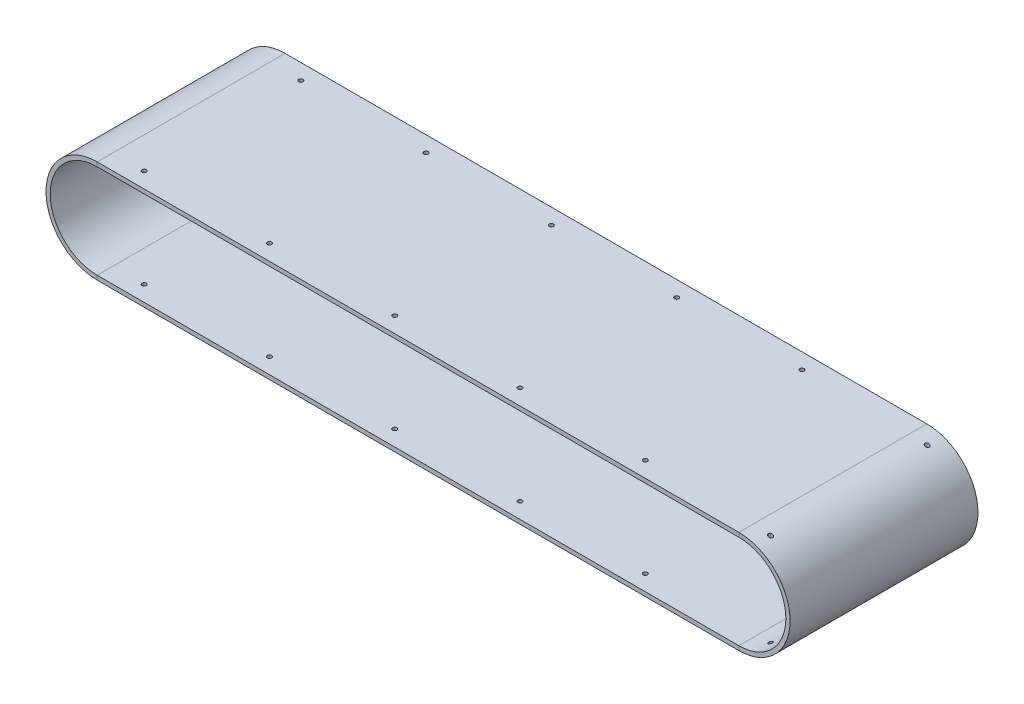
SolidWorks part; units mm, degrees
ref_plane "Front Plane" through (0, 0, 0) normal (0, 0, 1) x (1, 0, 0)
ref_plane "Top Plane" through (0, 0, 0) normal (0, 1, 0) x (1, 0, 0)
ref_plane "Right Plane" through (0, 0, 0) normal (1, 0, 0) x (0, 0, -1)
sketch "Sketch1" plane through (0, 0, 0) normal (0, 0, 1) x (1, 0, 0)
  line L0 (0, 39.8145) -> (520.371, 39.8145)
  line L1 (0, -39.8145) -> (520.371, -39.8145)
  line L2 (260.1855, 39.8145) -> (260.1855, -39.8145) construction
  arc A0 (0, 39.8145) -> (0, -39.8145) centre (0, 0) ccw
  arc A1 (520.371, 39.8145) -> (520.371, -39.8145) centre (520.371, 0) cw
  dimension "32" = 39.8145
  dimension "D2" = 300
sketch "Sketch2" plane through (0, 0, 0) normal (1, 0, 0) x (0, 0, -1)
  line L0 (0, 39.8145) -> (0, -39.8145) construction
  line L1 (-76.2, 38.1) -> (76.2, 38.1)
  line L2 (-76.2, 38.1) -> (-76.2, 41.529)
  line L3 (-76.2, 41.529) -> (76.2, 41.529)
  line L4 (76.2, 38.1) -> (76.2, 41.529)
  line L5 (-76.2, 38.1) -> (76.2, 41.529) construction
  line L6 (-76.2, 41.529) -> (76.2, 38.1) construction
  line L7 (0, 39.8145) -> (0, -39.8145) construction
  point P0 (0, 39.8145)
  dimension "D1" = 3.429
  dimension "D2" = 152.4
sweep "Sweep1" add profiles "Sketch2" path "Sketch1"
sketch "Sketch3" plane through (0, 41.529, 0) normal (0, 1, 0) x (1, 0, 0)
  line L0 (0, -63.5) -> (520.371, -63.5) construction
  line L1 (520.371, 76.2) -> (520.371, -76.2) construction
  line L2 (520.371, -76.2) -> (0, -76.2) construction
  line L3 (0, 76.2) -> (0, -76.2) construction
  line L4 (0, 0) -> (520.371, 0) construction
  circle A0 centre (25.4, -63.5) radius 1.75
  circle A1 centre (25.4, 63.5) radius 1.75
  circle A2 centre (127, -63.5) radius 1.75
  circle A3 centre (127, 63.5) radius 1.75
  circle A4 centre (228.6, -63.5) radius 1.75
  circle A5 centre (228.6, 63.5) radius 1.75
  circle A6 centre (330.2, -63.5) radius 1.75
  circle A7 centre (330.2, 63.5) radius 1.75
  circle A8 centre (431.8, -63.5) radius 1.75
  circle A9 centre (431.8, 63.5) radius 1.75
  circle A10 centre (533.4, -63.5) radius 1.75
  circle A11 centre (533.4, 63.5) radius 1.75
  dimension "D2" = 3.5
  dimension "D1" = 12.7
  dimension "D3" = 25.4
  dimension "D5" = 101.6
  dimension "D4" = 6
extrude "Cut-Extrude1" cut sketch "Sketch3" against normal through all
equation "\"D2@Sketch2\"=6in"
equation "\"32@Sketch1\"=1.5+0.135/2in"
